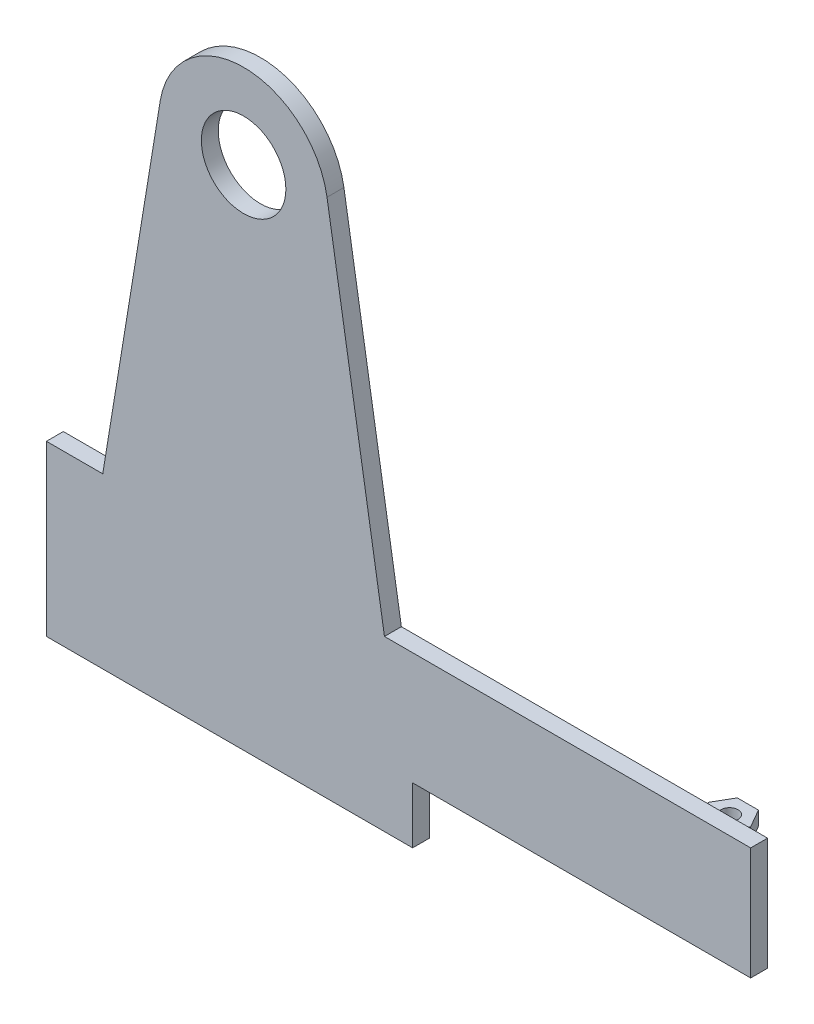
SolidWorks part; units mm, degrees
material "Сталь 3 ГОСТ 535-88"
ref_plane "Спереди" through (0, 0, 0) normal (0, 0, 1) x (1, 0, 0)
ref_plane "Сверху" through (0, 0, 0) normal (0, 1, 0) x (1, 0, 0)
ref_plane "Справа" through (0, 0, 0) normal (1, 0, 0) x (0, 0, -1)
sketch "Эскиз1" plane through (0, 0, 0) normal (0, 0, 1) x (1, 0, 0)
  line L0 (-65, 0) -> (-65, 60)
  line L1 (-65, 60) -> (185, 60)
  line L2 (185, 60) -> (185, 20)
  line L3 (185, 20) -> (65, 20)
  line L4 (65, 20) -> (65, 0)
  line L6 (65, 0) -> (-65, 0)
  dimension "D1" = 130
  dimension "D2" = 60
  dimension "D3" = 40
  dimension "D4" = 250
extrude "Бобышка-Вытянуть1" add sketch "Эскиз1" against normal blind 6
sketch "Эскиз2" plane through (0, 0, 0) normal (0, 0, 1) x (1, 0, 0)
  line L0 (-45, 60) -> (-24.6076, 184.8365)
  line L1 (185, 60) -> (-65, 60) construction
  line L2 (34.6076, 184.8365) -> (55, 60)
  line L3 (-45, 60) -> (55, 60)
  line L4 (5, 204.1229) -> (5, 138.6821) construction
  arc A0 (-24.6076, 184.8365) -> (34.6076, 184.8365) centre (5, 180) cw
  circle A1 centre (5, 180) radius 15
  point P6 (0, 0)
  point P12 (5, 60)
  dimension "D2" = 30
  dimension "D4" = 30
  dimension "D1" = 20
  dimension "D3" = 150
  dimension "D5" = 100
extrude "Бобышка-Вытянуть2" add sketch "Эскиз2" against normal blind 6
ref_plane "Плоскость1" through (0, 54, 0) normal (0, 1, 0) x (1, 0, 0)
sketch "Эскиз3" plane through (0, 54, 0) normal (0, 1, 0) x (1, 0, 0)
  line L0 (-65, 6) -> (65, 6) construction
  line L1 (157.4944, 12.5) -> (161.2472, 6)
  line L2 (161.2472, 6) -> (168.7528, 6)
  line L3 (168.7528, 6) -> (172.5056, 12.5)
  line L4 (172.5056, 12.5) -> (168.7528, 19)
  line L5 (168.7528, 19) -> (161.2472, 19)
  line L6 (161.2472, 19) -> (157.4944, 12.5)
  line L7 (185, 6) -> (185, 0) construction
  circle A0 centre (165, 12.5) radius 6.5 construction
  circle A1 centre (165, 12.5) radius 3
  dimension "D2" = 6
  dimension "D1" = 13
  dimension "D3" = 20
extrude "Бобышка-Вытянуть3" add sketch "Эскиз3" against normal blind 5 separate body
ref_plane "Плоскость2" through (60, 0, 0) normal (1, 0, 0) x (0, 0, -1)
mirror "Зеркальное отражение1" about plane through (60, 0, 0) normal (1, 0, 0) of bodies 105
